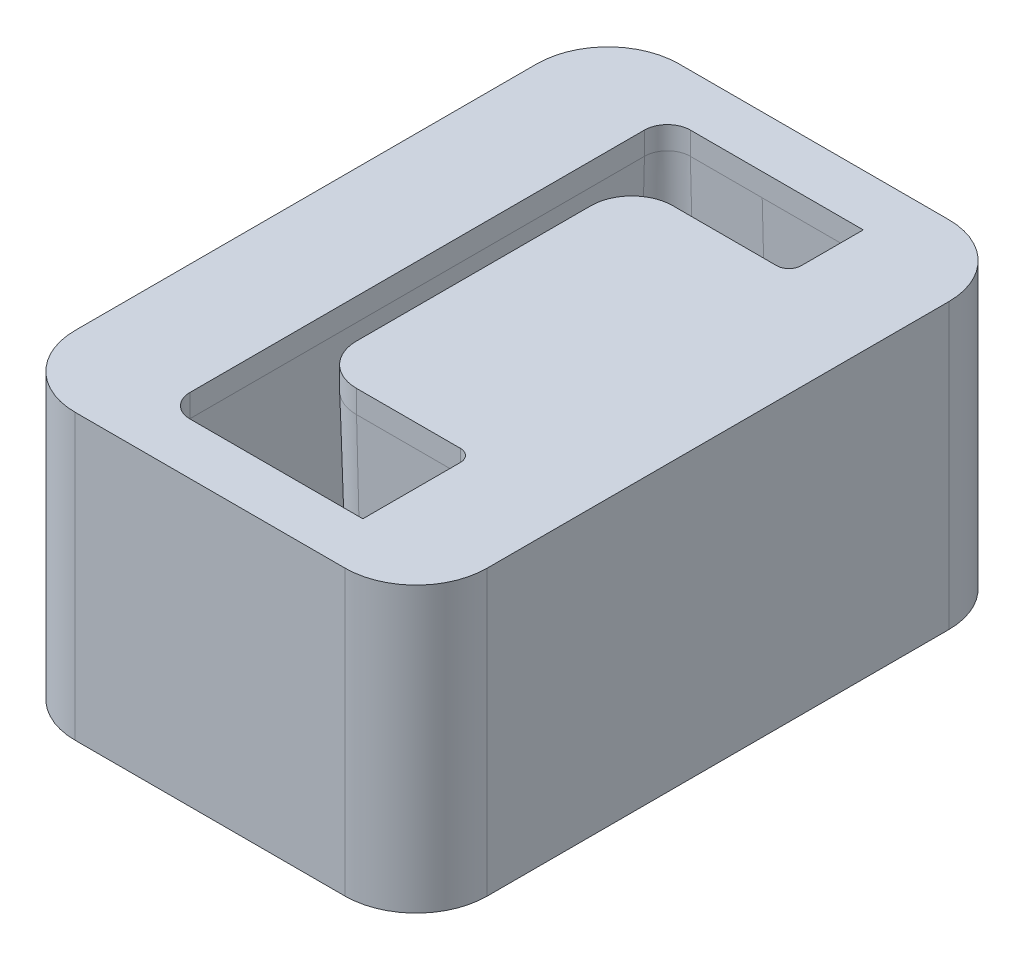
SolidWorks part; units mm, degrees
material "K110"
ref_plane "Front Plane" through (0, 0, 0) normal (0, 0, 1) x (1, 0, 0)
ref_plane "Top Plane" through (0, 0, 0) normal (0, 1, 0) x (1, 0, 0)
ref_plane "Right Plane" through (0, 0, 0) normal (1, 0, 0) x (0, 0, -1)
sketch "Sketch1" plane through (0, 0, 0) normal (0, 1, 0) x (1, 0, 0)
  line L1 (-29, -42.5) -> (29, -42.5)
  line L2 (-29, -42.5) -> (-29, 42.5)
  line L3 (-29, 42.5) -> (29, 42.5)
  line L4 (29, -42.5) -> (29, 42.5)
  line L5 (-29, -42.5) -> (29, 42.5) construction
  line L6 (-29, 42.5) -> (29, -42.5) construction
  point P0 (0, 0)
  dimension "D1" = 85
  dimension "D2" = 58
extrude "Boss-Extrude1" add sketch "Sketch1" against normal blind 40
fillet "Fillet1" radius 10 4 edges at (-29, -20, -42.5) (29, -20, -42.5) (29, -20, 42.5) (-29, -20, 42.5)
sketch "Sketch2" plane through (0, 0, 0) normal (0, 1, 0) x (1, 0, 0)
  line L16 (14.23, 35.23) -> (-10.12, 35.23)
  line L17 (-13.35, 32) -> (-13.35, -32)
  line L18 (-10.12, -35.23) -> (14.23, -35.23)
  line L19 (14.23, -35.23) -> (14.23, -21.5)
  line L20 (12.5, -19.77) -> (-2.12, -19.77)
  line L21 (-7.89, -14) -> (-7.89, 19)
  line L22 (-2.12, 24.77) -> (12.5, 24.77)
  line L23 (14.23, 26.5) -> (14.23, 35.23)
  line L24 (14.23, 35.23) -> (-10.12, 35.23)
  line L25 (-13.35, 32) -> (-13.35, -32)
  line L26 (-10.12, -35.23) -> (14.23, -35.23)
  line L27 (14.23, -35.23) -> (14.23, -21.5)
  line L28 (12.5, -19.77) -> (-2.12, -19.77)
  line L29 (-7.89, -14) -> (-7.89, 19)
  line L30 (-2.12, 24.77) -> (12.5, 24.77)
  line L31 (14.23, 26.5) -> (14.23, 35.23)
  arc A12 (-10.12, 35.23) -> (-13.35, 32) centre (-10.12, 32) ccw
  arc A13 (-13.35, -32) -> (-10.12, -35.23) centre (-10.12, -32) ccw
  arc A14 (14.23, -21.5) -> (12.5, -19.77) centre (12.5, -21.5) ccw
  arc A15 (-7.89, -14) -> (-2.12, -19.77) centre (-2.12, -14) ccw
  arc A16 (-2.12, 24.77) -> (-7.89, 19) centre (-2.12, 19) ccw
  arc A17 (12.5, 24.77) -> (14.23, 26.5) centre (12.5, 26.5) ccw
  arc A18 (-10.12, 35.23) -> (-13.35, 32) centre (-10.12, 32) ccw
  arc A19 (-13.35, -32) -> (-10.12, -35.23) centre (-10.12, -32) ccw
  arc A20 (14.23, -21.5) -> (12.5, -19.77) centre (12.5, -21.5) ccw
  arc A21 (-7.89, -14) -> (-2.12, -19.77) centre (-2.12, -14) ccw
  arc A22 (-2.12, 24.77) -> (-7.89, 19) centre (-2.12, 19) ccw
  arc A23 (12.5, 24.77) -> (14.23, 26.5) centre (12.5, 26.5) ccw
  dimension "D1" = 0.23
extrude "Cut-Extrude1" cut sketch "Sketch2" against normal up to next
sketch "Sketch3" plane through (0, 0, 0) normal (1, 0, 0) x (0, 0, -1)
  line L0 (35.23, -3.2) -> (36.1936, -40)
  line L1 (35.23, -40) -> (35.23, 0) construction
  line L2 (32.5, -40) -> (42.5, -40) construction
  line L3 (36.1936, -40) -> (35.23, -40)
  line L4 (35.23, -40) -> (35.23, -3.2)
  line L5 (31.9, 0) -> (-31.9, 0) construction
  dimension "D1" = 3.2
  dimension "D2" = 1.5
sketch "Sketch5" plane through (0, 0, 0) normal (0, 1, 0) x (1, 0, 0)
  line L0 (12.5, -19.77) -> (-2.12, -19.77) construction
  line L1 (14.23, -35.23) -> (14.23, -21.5) construction
  line L2 (-10.12, -35.23) -> (14.23, -35.23) construction
  line L3 (-7.89, -14) -> (-7.89, 19) construction
  line L4 (-2.12, 24.77) -> (12.5, 24.77) construction
  line L5 (-13.35, 32) -> (-13.35, -32) construction
  line L6 (14.23, 35.23) -> (-10.12, 35.23) construction
  line L7 (14.23, 26.5) -> (14.23, 35.23) construction
  line L8 (12.5, -19.77) -> (-2.12, -19.77)
  line L9 (14.23, -35.23) -> (14.23, -21.5)
  line L10 (-10.12, -35.23) -> (14.23, -35.23)
  line L11 (-7.89, -14) -> (-7.89, 19)
  line L12 (-2.12, 24.77) -> (12.5, 24.77)
  line L13 (-13.35, 32) -> (-13.35, -32)
  line L14 (14.23, 35.23) -> (-10.12, 35.23)
  line L15 (14.23, 26.5) -> (14.23, 35.23)
  arc A0 (-7.89, -14) -> (-2.12, -19.77) centre (-2.12, -14) ccw construction
  arc A1 (14.23, -21.5) -> (12.5, -19.77) centre (12.5, -21.5) ccw construction
  arc A2 (-13.35, -32) -> (-10.12, -35.23) centre (-10.12, -32) ccw construction
  arc A3 (-2.12, 24.77) -> (-7.89, 19) centre (-2.12, 19) ccw construction
  arc A4 (-10.12, 35.23) -> (-13.35, 32) centre (-10.12, 32) ccw construction
  arc A5 (12.5, 24.77) -> (14.23, 26.5) centre (12.5, 26.5) ccw construction
  arc A6 (-7.89, -14) -> (-2.12, -19.77) centre (-2.12, -14) ccw
  arc A7 (14.23, -21.5) -> (12.5, -19.77) centre (12.5, -21.5) ccw
  arc A8 (-13.35, -32) -> (-10.12, -35.23) centre (-10.12, -32) ccw
  arc A9 (-2.12, 24.77) -> (-7.89, 19) centre (-2.12, 19) ccw
  arc A10 (-10.12, 35.23) -> (-13.35, 32) centre (-10.12, 32) ccw
  arc A11 (12.5, 24.77) -> (14.23, 26.5) centre (12.5, 26.5) ccw
sweep "Cut-Sweep1" cut profiles "Sketch3" path "Sketch5"
hole_wizard "M6 Tapped Hole1" positions "Sketch8" profile "Sketch7" tap size "M6" standard "ISO"
sketch "Sketch8" plane through (0, -40, 0) normal (0, -1, 0) x (-1, 0, 0)
  line L0 (-19, 42.5) -> (19, 42.5) construction
  line L1 (-29, -32.5) -> (-29, 32.5) construction
  line L2 (29, 32.5) -> (29, -32.5) construction
  line L3 (19, -42.5) -> (-19, -42.5) construction
  point P0 (-22, 35.5)
  point P2 (22, 35.5)
  point P4 (22, -35.5)
  point P6 (-22, -35.5)
  dimension "D1" = 7
  dimension "D2" = 7
  dimension "D3" = 7
  dimension "D4" = 7
sketch "Sketch7" plane through (22, -40, -35.5) normal (1, 0, 0) x (0, 0, -1)
  line L0 (0, 0) -> (0, 18.5022)
  line L1 (0, 18.5022) -> (2.5, 17)
  line L2 (2.5, 17) -> (2.5, 0.525)
  line L3 (2.5, 0.525) -> (3.025, 0)
  line L5 (3.025, 0) -> (0, 0)
  line L6 (-2.5, 0.525) -> (-3.025, 0) construction
  line L10 (0, 18.5022) -> (-2.5, 17) construction
  line L11 (0, -6.35) -> (0, 107.95) construction
  dimension "Tap Drill Dia." = 5
  dimension "Tap Drill Depth" = 17
  dimension "Near C'Sink Dia." = 6.05
  dimension "Near C'Sink Angle" = 90
  dimension "Drill Angle" = 118
cosmetic thread "Hole Thread1"
cosmetic thread "Hole Thread2"
cosmetic thread "Hole Thread3"
cosmetic thread "Hole Thread4"
